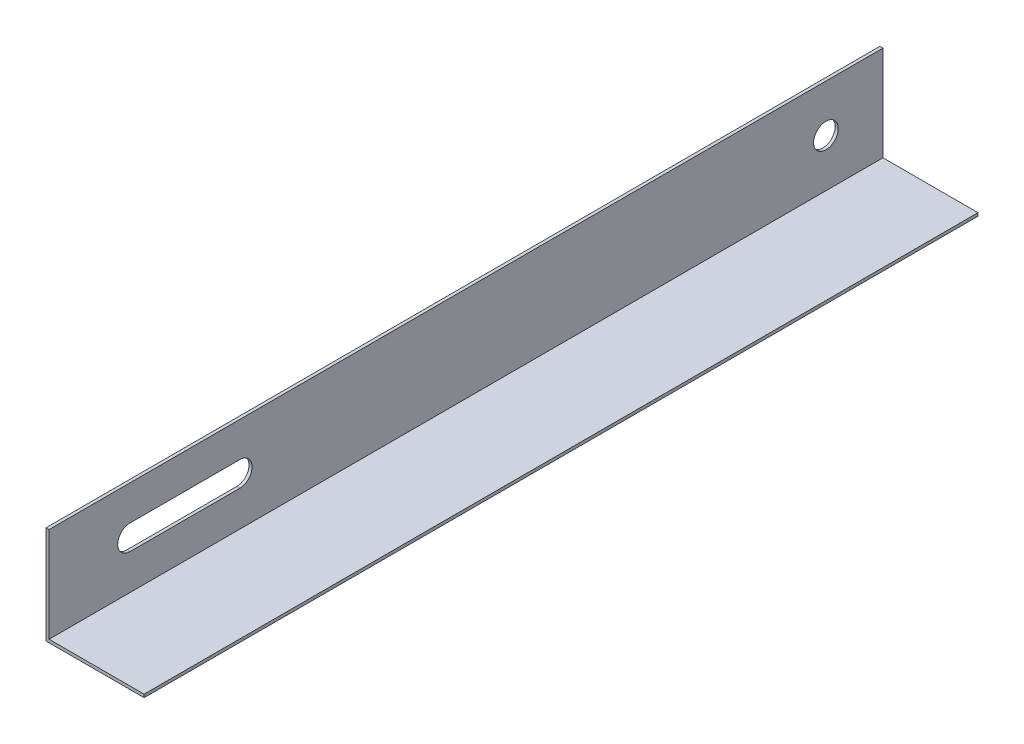
SolidWorks part; units mm, degrees
ref_plane "Front Plane" through (0, 0, 0) normal (0, 0, 1) x (1, 0, 0)
ref_plane "Top Plane" through (0, 0, 0) normal (0, 1, 0) x (1, 0, 0)
ref_plane "Right Plane" through (0, 0, 0) normal (1, 0, 0) x (0, 0, -1)
sketch "Sketch3" plane through (0, 0, 0) normal (0, 0, 1) x (1, 0, 0)
  line L0 (0, 0) -> (0, 49.2125)
  line L1 (0, 49.2125) -> (-1.5875, 49.2125)
  line L2 (-1.5875, 49.2125) -> (-1.5875, -1.5875)
  line L3 (-1.5875, -1.5875) -> (49.2125, -1.5875)
  line L4 (49.2125, -1.5875) -> (49.2125, 0)
  line L5 (49.2125, 0) -> (0, 0)
  dimension "D1" = 1.5875
  dimension "D2" = 1.5875
  dimension "D3" = 50.8
  dimension "D4" = 50.8
extrude "Boss-Extrude2" add sketch "Sketch3" along normal blind 431.8
sketch "Sketch6" plane through (0, 0, 0) normal (1, 0, 0) x (0, 0, -1)
  line L0 (-389.8475, 24.7736) -> (-333.0938, 24.7736) construction
  line L1 (-389.8475, 31.1871) -> (-333.0938, 31.1871)
  line L2 (-389.8475, 18.3601) -> (-333.0938, 18.3601)
  arc A0 (-389.8475, 31.1871) -> (-389.8475, 18.3601) centre (-389.8475, 24.7736) ccw
  arc A1 (-333.0938, 18.3601) -> (-333.0938, 31.1871) centre (-333.0938, 24.7736) ccw
  point P2 (-361.4706, 24.7736)
  dimension "D1" = 12.827
extrude "Cut-Extrude3" cut sketch "Sketch6" against normal blind 127
sketch "Sketch7" plane through (0, 0, 0) normal (1, 0, 0) x (0, 0, -1)
  circle A0 centre (-29.5388, 24.7736) radius 6.3881
  dimension "D1" = 12.7762
extrude "Cut-Extrude4" cut sketch "Sketch7" against normal blind 127
